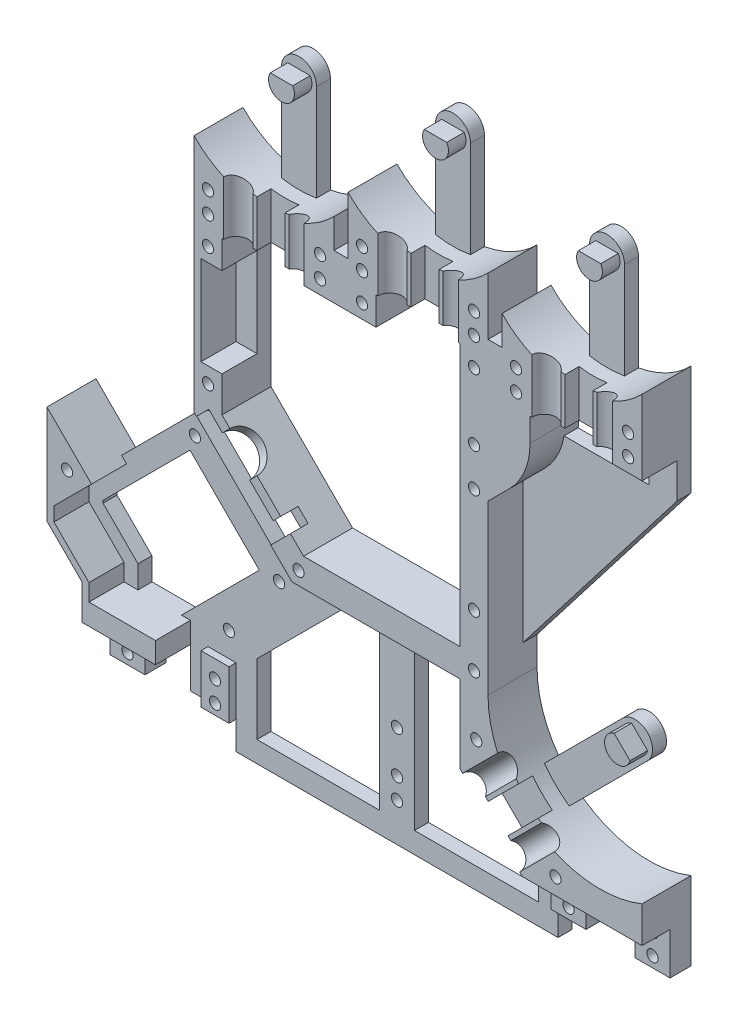
SolidWorks part; units mm, degrees
ref_plane "Front" through (0, 0, 0) normal (0, 0, 1) x (1, 0, 0)
ref_plane "Top" through (0, 0, 0) normal (0, 1, 0) x (1, 0, 0)
ref_plane "Right" through (0, 0, 0) normal (1, 0, 0) x (0, 0, -1)
sketch "Sketch1" plane through (0, 0, 0) normal (0, 0, 1) x (1, 0, 0)
  line L0 (47, 67.5) -> (47, 71.5)
  line L1 (47, 71.5) -> (59, 71.5)
  line L2 (69, 67.5) -> (69, 62.5)
  line L3 (85, 10) -> (85, 15.1676)
  line L4 (67.8873, 10) -> (85, 10)
  line L5 (69, 67.5) -> (81, 67.5)
  line L6 (59, 71.5) -> (59, 34)
  line L7 (36.6568, 34) -> (59, 34)
  line L8 (5, 10) -> (5, 15)
  line L9 (15.4289, 34.0147) -> (3, 21.5858)
  line L10 (0, 34.1421) -> (0, 20)
  line L11 (25, 67.5) -> (25, 45.6568)
  line L12 (25, 45.6568) -> (36.6568, 34)
  line L13 (0, 20) -> (5, 15)
  line L14 (8, 13) -> (14.2134, 13)
  line L15 (25.3285, 24.1151) -> (14.2134, 13)
  line L16 (3, 21.2426) -> (3, 21.5858)
  line L17 (8, 13) -> (8, 16.2426)
  line L18 (81, 67.5) -> (81, 62.5)
  line L20 (3, 21.2426) -> (8, 16.2426)
  line L21 (81, 62.5) -> (69, 62.5)
  line L22 (65.2114, 12.6759) -> (59, 18.8873)
  line L24 (59, 18.8873) -> (59, 30)
  line L25 (47.5, 30) -> (59, 30)
  line L26 (63, 34) -> (85, 62.5)
  line L27 (65.2114, 3) -> (65.2114, 12.6759)
  line L30 (85, 71.5) -> (85, 62.5)
  line L31 (63, 34) -> (63, 30)
  line L77 (5.6569, 28.4853) -> (0, 34.1421)
  line L82 (25, 3) -> (25, 13)
  line L83 (22, 10) -> (5, 10)
  line L89 (16.136, 38.9644) -> (5.6569, 28.4853)
  line L109 (28.1568, 26.9436) -> (16.136, 38.9644)
  line L120 (21, 71.5) -> (21, 43.9999)
  line L127 (68, 0) -> (22, 0)
  line L129 (15.4289, 34.0147) -> (25.3285, 24.1151)
  line L132 (21, 43.9999) -> (33.1066, 31.8933)
  line L133 (21, 71.5) -> (43, 71.5)
  line L134 (25, 13) -> (42, 30)
  line L135 (22, 0) -> (22, 10)
  line L136 (68, 10) -> (68, 0)
  line L137 (85, 10) -> (68, 10)
  line L138 (25, 67.5) -> (47, 67.5)
  line L140 (43, 71.5) -> (43, 75.5)
  line L143 (42, 30) -> (42.5, 30)
  line L144 (63, 71.5) -> (85, 71.5)
  line L145 (63, 75.5) -> (63, 71.5)
  line L148 (33.1066, 31.8933) -> (28.1568, 26.9436)
  line L150 (47.5, 30) -> (47.5, 3)
  line L152 (42.5, 30) -> (42.5, 3)
  line L153 (43, 75.5) -> (63, 75.5)
  line L156 (47.5, 3) -> (65.2114, 3)
  line L157 (25, 3) -> (42.5, 3)
  line L160 (22, 0) -> (0, 0) construction
  arc A0 (63, 30) -> (85, 15.1676) centre (79, 30) ccw
extrude "Boss-Extrude1" add sketch "Sketch1" along normal blind 2 contours L83 L135 L127 L136 L137 L144 L145 L153 L140 L133 L120 L132 L148 L109 L89 L77 L157 L82 L134 L143 L152 L156 L150 L138 L129 region at (76.5, 11.1369, 0)
sketch "Sketch5" plane through (0, 0, 0) normal (0, 0, 1) x (1, 0, 0)
  line L0 (21, 78.202) -> (21, 43.9999)
  line L1 (63, 74) -> (65, 74)
  line L2 (80, 0) -> (73, 0) construction
  line L3 (15.5, 11) -> (15.5, 13)
  line L4 (43, 74) -> (43, 82.202)
  line L5 (63, 74) -> (63, 82.202)
  line L6 (69, 67.5) -> (85, 67.5)
  line L7 (5, 4) -> (5, 15)
  line L8 (22, 63.5) -> (22, 50.7322)
  line L9 (59, 30) -> (59, 18.8873)
  line L10 (53, 78) -> (53, 92) construction
  line L11 (25, 45.6568) -> (36.6568, 34)
  line L12 (12.6005, 43.2071) -> (12.2469, 43.5607) construction
  line L13 (32.3995, 31.8934) -> (16.8431, 47.4498) construction
  line L14 (15.5, 13) -> (6, 13)
  line L15 (0, 20) -> (5, 15)
  line L16 (73, 0) -> (73, -10) construction
  line L17 (17, 0) -> (17, -10) construction
  line L18 (12.2469, 43.5607) -> (2.3474, 33.6612) construction
  line L19 (73, -10) -> (68, -10) construction
  line L20 (28.1568, 27.6508) -> (12.6005, 43.2071) construction
  line L21 (68, -10) -> (68, 0) construction
  line L22 (0, 34.1422) -> (6.364, 27.7783)
  line L23 (0, 34.1422) -> (0, 20)
  line L24 (6, 13) -> (6, 15.4142)
  line L25 (19, 64.2929) -> (-1, 64.2929) construction
  line L26 (17, -10) -> (22, -10) construction
  line L27 (85, 0) -> (85, -10) construction
  line L28 (-1, 37.0086) -> (-1, 64.2929) construction
  line L29 (5, 4) -> (10, 4)
  line L30 (22, -10) -> (22, 0) construction
  line L31 (85, -10) -> (80, -10) construction
  line L32 (0, 0) -> (5, 0) construction
  line L33 (10, 4) -> (10, 10)
  line L34 (80, -10) -> (80, 0) construction
  line L35 (34.9999, 30) -> (59, 30)
  line L36 (80, 0) -> (85, 0) construction
  line L37 (85, 4) -> (80, 4)
  line L38 (22, 4) -> (22, 11)
  line L39 (10, 10) -> (15.5, 10)
  line L40 (15.5, 10) -> (15.5, 4)
  line L41 (42.5, 10) -> (47.5, 10) construction
  line L42 (80, 4) -> (80, 10)
  line L43 (31, 74) -> (31, 88) construction
  line L44 (10, 0) -> (17, 0) construction
  line L45 (17, 0) -> (22, 0) construction
  line L46 (34.9999, 30) -> (21, 43.9999)
  line L47 (36.6568, 34) -> (59, 34)
  line L48 (73, 10) -> (73, 4)
  line L49 (80, 10) -> (73, 10)
  line L50 (73, 4) -> (68, 4)
  line L51 (85, 67.5) -> (85, 78.202)
  line L52 (73, 0) -> (68, 0) construction
  line L53 (2.3474, 33.6612) -> (-1, 37.0086) construction
  line L54 (28.1568, 27.6508) -> (32.3995, 31.8934) construction
  line L55 (15.5, 4) -> (22, 4)
  line L56 (59, 18.8873) -> (65.2114, 12.6759)
  line L57 (42.5, 0) -> (42.5, 10) construction
  line L58 (42.5, 0) -> (42.5, -10) construction
  line L59 (65.2114, 12.6759) -> (68, 9.8873)
  line L60 (59, 34) -> (59, 71.5)
  line L61 (42.5, 10) -> (47.5, 10) construction
  line L62 (47.5, -10) -> (47.5, 0) construction
  line L63 (47.5, 10) -> (47.5, 0) construction
  line L64 (42.5, -10) -> (47.5, -10) construction
  line L65 (15.5, 11) -> (22, 11)
  line L66 (25, 67.5) -> (47, 67.5)
  line L67 (47, 67.5) -> (47, 71.5)
  line L68 (19, 45.2929) -> (19, 64.2929) construction
  line L69 (25, 45.6568) -> (25, 50.7322)
  line L70 (63, 54) -> (63, 30)
  line L71 (25, 67.5) -> (25, 63.5)
  line L72 (25, 63.5) -> (22, 63.5)
  line L74 (25, 50.7322) -> (22, 50.7322)
  line L75 (68, 9.8873) -> (68, 4)
  line L76 (41, 74) -> (43, 74)
  line L79 (47, 71.5) -> (59, 71.5)
  line L80 (69, 67.5) -> (69, 60)
  line L82 (6.364, 27.7783) -> (1, 22.4143)
  line L83 (85, 15.1676) -> (85, 10)
  line L85 (85, 0) -> (80, 0) construction
  line L86 (85, 0) -> (85, -10) construction
  line L87 (1, 20.4142) -> (6, 15.4142)
  line L88 (42.5, -10) -> (47.5, -10) construction
  line L89 (80, 0) -> (73, 0) construction
  line L90 (85, -10) -> (80, -10) construction
  line L91 (80, -10) -> (80, 0) construction
  line L93 (5, 0) -> (5, -10) construction
  line L94 (68, -10) -> (68, 0) construction
  line L95 (41, 78.202) -> (41, 74)
  line L96 (5, -10) -> (10, -10) construction
  line L97 (73, 0) -> (73, -10) construction
  line L98 (73, -10) -> (68, -10) construction
  line L99 (10, -10) -> (10, 0) construction
  line L100 (10, 0) -> (5, 0) construction
  line L101 (5, 0) -> (10, 0) construction
  line L102 (10, 0) -> (17, 0) construction
  line L103 (73, 0) -> (68, 0) construction
  line L104 (75, 74) -> (75, 88) construction
  line L105 (65, 74) -> (65, 78.202)
  line L106 (22, -10) -> (17, -10) construction
  line L107 (17, -10) -> (17, 0) construction
  line L108 (1, 22.4143) -> (1, 20.4142)
  line L109 (22, 0) -> (17, 0) construction
  line L110 (22, -10) -> (22, 0) construction
  line L111 (68, 0) -> (47.5, 0) construction
  line L112 (47.5, 0) -> (47.5, -10) construction
  line L113 (42.5, -10) -> (42.5, 0) construction
  line L114 (42.5, 0) -> (22, 0) construction
  line L115 (63, 54) -> (69, 60)
  line L116 (85, 10) -> (85, 4)
  arc A0 (21, 78.202) -> (41, 78.202) centre (31, 88) ccw
  arc A1 (43, 82.202) -> (63, 82.202) centre (53, 92) ccw
  arc A2 (65, 78.202) -> (85, 78.202) centre (75, 88) ccw
  arc A3 (63, 30) -> (85, 15.1676) centre (79, 30) ccw
extrude "Boss-Extrude2" add sketch "Sketch5" along normal blind 7 contours A2 L105 L1 L5 A1 L4 L76 L95 A0 L51 L79 L60 L74 L8 L72 L71 | L108 L23 L15 L7 L29 L33 L39 L40 L55 L38 L87 | L50 L48 L49 L42 L37 region at (31, 72.9895, 0) region at (18.75, 10.6268, 0)
sketch "Sketch33" plane through (0, 0, 0) normal (0, 0, 1) x (1, 0, 0)
  line L1 (31, 74) -> (31, 67.5) construction
  line L2 (31, 74) -> (31, 67.5) construction
  line L3 (75, 74) -> (75, 67.5) construction
  line L4 (31, 67.5) -> (33.5, 67.5)
  line L5 (75, 67.5) -> (77.5, 67.5)
  line L6 (77.5, 67.5) -> (77.5, 88)
  line L7 (75, 67.5) -> (72.5, 67.5)
  line L8 (72.5, 67.5) -> (72.5, 88)
  line L9 (77.2322, 31.7678) -> (61.6759, 16.2114)
  line L11 (61.6759, 16.2114) -> (65.2114, 12.6759)
  line L13 (53, 78) -> (53, 71.5) construction
  line L14 (53, 71.5) -> (55.5, 71.5)
  line L15 (55.5, 71.5) -> (55.5, 92)
  line L16 (53, 71.5) -> (50.5, 71.5)
  line L17 (50.5, 71.5) -> (50.5, 92)
  line L18 (33.5, 67.5) -> (33.5, 88)
  line L19 (31, 67.5) -> (28.5, 67.5)
  line L20 (28.5, 67.5) -> (28.5, 88)
  line L21 (65.2114, 12.6759) -> (80.7678, 28.2322)
  arc A0 (77.5, 88) -> (72.5, 88) centre (75, 88) ccw
  arc A1 (55.5, 92) -> (50.5, 92) centre (53, 92) ccw
  arc A2 (33.5, 88) -> (28.5, 88) centre (31, 88) ccw
  arc A3 (80.7678, 28.2322) -> (77.2322, 31.7678) centre (79, 30) ccw
extrude "Boss-Extrude3" add sketch "Sketch33" along normal blind 2
sketch "Sketch34" plane through (0, 0, 0) normal (0, 0, 1) x (1, 0, 0)
  line L0 (31, 88) -> (31, 88.925) construction
  line L1 (29.3979, 88.925) -> (32.6021, 88.925)
  line L2 (53, 92) -> (53, 92.925) construction
  line L3 (51.3979, 92.925) -> (54.6021, 92.925)
  line L4 (75, 88) -> (75, 88.925) construction
  line L5 (73.3979, 88.925) -> (76.6021, 88.925)
  line L6 (79, 30) -> (79.6541, 30.6541) construction
  line L7 (78.5212, 31.787) -> (80.787, 29.5212)
  arc A0 (78.5212, 31.787) -> (80.787, 29.5212) centre (79, 30) ccw
  arc A3 (29.3979, 88.925) -> (32.6021, 88.925) centre (31, 88) ccw
  arc A4 (51.3979, 92.925) -> (54.6021, 92.925) centre (53, 92) ccw
  arc A5 (73.3979, 88.925) -> (76.6021, 88.925) centre (75, 88) ccw
extrude "Boss-Extrude4" add sketch "Sketch34" along normal blind 2.5 from offset 2
sketch "Sketch10" plane through (0, 0, 0) normal (0, 1, 0) x (1, 0, 0)
  line L0 (49, -7) -> (57, -7)
  line L1 (27, -6) -> (29, -6)
  line L2 (35, -7) -> (35, -6)
  line L3 (27, -7) -> (35, -7)
  line L4 (71, -7) -> (79, -7)
  line L5 (49, -6) -> (51, -6)
  line L6 (27, -6) -> (27, -7)
  line L7 (29, -6) -> (29, -4)
  line L8 (29, -4) -> (33, -4)
  line L9 (57, -7) -> (57, -6)
  line L10 (33, -4) -> (33, -6)
  line L11 (71, -6) -> (73, -6)
  line L12 (33, -6) -> (35, -6)
  line L13 (51, -6) -> (51, -4)
  line L14 (51, -4) -> (55, -4)
  line L15 (55, -4) -> (55, -6)
  line L16 (55, -6) -> (57, -6)
  line L17 (73, -6) -> (73, -4)
  line L18 (73, -4) -> (77, -4)
  line L19 (77, -4) -> (77, -6)
  line L20 (77, -6) -> (79, -6)
  line L23 (49, -6) -> (49, -7)
  line L32 (79, -7) -> (79, -6)
  line L47 (71, -6) -> (71, -7)
  circle A0 centre (27, -7) radius 1.75
  circle A1 centre (35, -7) radius 1.75
  circle A2 centre (49, -7) radius 1.75
  circle A3 centre (57, -7) radius 1.75
  circle A4 centre (71, -7) radius 1.75
  circle A5 centre (79, -7) radius 1.75
extrude "Wire and Tube Canals" cut sketch "Sketch10" along normal blind 13 from offset 67.5 contours A0 | A1 | A2 | A3 | A4 | A5 | A3 A2 L0 | A5 A4 L4 | L3 L2 L12 L10 L8 L7 L1 L6 region at (48.8288, 0, 7.1002) region at (53, 0, 5.5512) region at (57.1712, 0, 7.1002) region at (26.8288, 0, 7.1002) region at (35.1712, 0, 7.1002) region at (70.8288, 0, 7.1002) region at (75, 0, 5.5512) region at (79.1712, 0, 7.1002) body kept at (59, 30, 0)
sketch "Sketch42" plane through (0, 0, 0) normal (0, 0, 1) x (1, 0, 0)
  line L1 (5, 4) -> (10, 4)
  line L2 (5, 4) -> (5, 10)
  line L3 (5, 10) -> (10, 10)
  line L4 (10, 4) -> (10, 10)
  line L5 (15.5, 4) -> (22, 4)
  line L6 (15.5, 4) -> (15.5, 11)
  line L7 (15.5, 11) -> (22, 11)
  line L8 (22, 4) -> (22, 11)
  line L10 (67, 4) -> (73, 4)
  line L11 (67, 4) -> (67, 10)
  line L12 (67, 10) -> (73, 10)
  line L13 (73, 4) -> (73, 10)
  line L14 (80, 4) -> (85, 4)
  line L15 (80, 4) -> (80, 10)
  line L16 (80, 10) -> (85, 10)
  line L17 (85, 4) -> (85, 10)
extrude "Cut-Extrude3" cut sketch "Sketch42" along normal blind 4 from offset 3
fillet "Fillet1" radius 10 1 edges at (69, 60, 4.5)
sketch "Sketch35" plane through (32.4999, 32.4999, 0) normal (-0.7071, -0.7071, 0) x (0, 0, 1)
  line L0 (7, 15.7634) -> (7, 10.2634) construction
  line L1 (7, 10.2634) -> (7, 0.7634) construction
  line L2 (7, 10.2634) -> (12.5, 10.2634) construction
  line L3 (7, 10.2634) -> (1.5, 10.2634) construction
  line L4 (5.5, 15.7634) -> (5.5, 14.2634) construction
  line L5 (5.5, 14.2634) -> (2.5, 14.2634) construction
  line L6 (5.5, 15.7634) -> (2.5, 14.2634)
  line L7 (2.5, 14.2634) -> (1.5, 14.2634)
  line L8 (1.5, 14.2634) -> (1.5, 10.2634)
  line L9 (1.5, 10.2634) -> (1.5, 6.0134)
  line L10 (1.5, 6.0134) -> (2.5, 6.0134)
  line L11 (2.5, 6.0134) -> (2.5, 0.7634)
  line L12 (2.5, 0.7634) -> (7, 0.7634)
  line L13 (8.5, 15.7634) -> (8.5, 14.2634) construction
  line L14 (8.5, 14.2634) -> (11.5, 14.2634) construction
  line L15 (8.5, 15.7634) -> (11.5, 14.2634)
  line L16 (11.5, 14.2634) -> (12.5, 14.2634)
  line L17 (12.5, 14.2634) -> (12.5, 10.2634)
  line L18 (12.5, 10.2634) -> (12.5, 6.0134)
  line L19 (12.5, 6.0134) -> (11.5, 6.0134)
  line L20 (11.5, 6.0134) -> (11.5, 0.7634)
  line L21 (11.5, 0.7634) -> (7, 0.7634)
  line L22 (12, 10.2634) -> (7, 10.2634) construction
  line L23 (8.5, 15.7634) -> (7, 15.7634)
  line L24 (7, 15.7634) -> (5.5, 15.7634)
  line L25 (7, 15.7634) -> (7, 16.2634) construction
  line L26 (2, 10.2634) -> (7, 10.2634) construction
extrude "Pot Insert1" cut sketch "Sketch35" against normal blind 2.5
sketch "Sketch36" plane through (32.4999, 32.4999, 0) normal (-0.7071, -0.7071, 0) x (0, 0, 1)
  line L0 (7, 16.2634) -> (7, 10.2634) construction
  line L1 (7, 10.2634) -> (7, 0.7634) construction
  line L2 (7, 0.7634) -> (4.5, 0.7634)
  line L5 (4.5, 0.7634) -> (4.5, 2.7634)
  line L6 (7, 0.7634) -> (9.5, 0.7634)
  line L7 (9.5, 0.7634) -> (9.5, 2.7634)
  line L8 (9.5, 2.7634) -> (4.5, 2.7634)
  circle A0 centre (7, 10.2634) radius 2.75
extrude "Pot Hole" cut sketch "Sketch36" against normal blind 1.5 from offset 2.5
sketch "Sketch43" plane through (15.5, 0, 0) normal (-1, 0, 0) x (0, 0, 1)
  line L0 (6.5, -5.5) -> (6.5, 0) construction
  line L1 (6.5, 0) -> (6.5, 11) construction
  line L2 (6.5, 0) -> (1, 0) construction
  line L3 (6.5, 0) -> (12, 0) construction
  line L4 (8, -5.5) -> (8, -4) construction
  line L5 (8, -4) -> (11, -4) construction
  line L6 (8, -5.5) -> (11, -4)
  line L7 (11, -4) -> (12, -4)
  line L8 (12, -4) -> (12, 0)
  line L9 (12, 0) -> (12, 5.25)
  line L10 (12, 5.25) -> (11, 5.25)
  line L11 (11, 5.25) -> (11, 11)
  line L12 (11, 11) -> (6.5, 11)
  line L13 (5, -5.5) -> (5, -4) construction
  line L14 (5, -4) -> (2, -4) construction
  line L15 (5, -5.5) -> (2, -4)
  line L16 (2, -4) -> (1, -4)
  line L17 (1, -4) -> (1, 0)
  line L18 (1, 0) -> (1, 4.25)
  line L19 (1, 4.25) -> (2, 4.25)
  line L20 (2, 4.25) -> (2, 11)
  line L21 (2, 11) -> (6.5, 11)
  line L22 (1.5, 0) -> (6.5, 0) construction
  line L23 (5, -5.5) -> (6.5, -5.5)
  line L24 (6.5, -5.5) -> (8, -5.5)
  line L25 (11.5, 0) -> (6.5, 0) construction
extrude "Pot Insert2" cut sketch "Sketch43" against normal blind 2.5
sketch "Sketch3" plane through (0, 0, 0) normal (0, 0, 1) x (1, 0, 0)
  line L0 (31, 72.5) -> (31, 69.5) construction
  line L1 (31, 69.5) -> (31, 65.5) construction
  line L2 (75, 69.5) -> (75, 65.5) construction
  line L3 (31, 65.5) -> (23, 65.5) construction
  line L4 (33.1066, 31.8933) -> (34.5208, 30.4791) construction
  line L5 (53, 69.5) -> (45, 69.5) construction
  line L6 (53, 73.5) -> (53, 69.5) construction
  line L7 (53, 69.5) -> (61, 69.5) construction
  line L9 (67.6863, 18.6863) -> (66.9792, 17.9792) construction
  line L10 (53, 69.5) -> (53, 54.5) construction
  line L11 (75, 65.5) -> (75, 48.75) construction
  line L12 (66.9792, 17.9792) -> (61.3223, 23.636) construction
  line L13 (31, 69.5) -> (39, 69.5) construction
  line L14 (66.9792, 17.9792) -> (72.636, 12.3223) construction
  line L15 (53, 76.5) -> (53, 73.5) construction
  line L16 (16.136, 38.9645) -> (17.5502, 37.5503) construction
  line L17 (75, 74) -> (75, 72.5) construction
  line L18 (75, 72.5) -> (83, 72.5) construction
  line L19 (75, 72.5) -> (67, 72.5) construction
  line L20 (34.5208, 30.4791) -> (35.935, 31.8933) construction
  line L21 (53, 76.5) -> (61, 76.5) construction
  line L22 (53, 76.5) -> (45, 76.5) construction
  line L23 (31, 74) -> (31, 72.5) construction
  line L24 (31, 72.5) -> (39, 72.5) construction
  line L25 (31, 72.5) -> (23, 72.5) construction
  line L26 (75, 72.5) -> (75, 69.5) construction
  line L27 (75, 69.5) -> (83, 69.5) construction
  line L28 (75, 69.5) -> (67, 69.5) construction
  line L29 (53, 73.5) -> (61, 73.5) construction
  line L30 (53, 73.5) -> (45, 73.5) construction
  line L31 (31, 69.5) -> (23, 69.5) construction
  line L32 (53, 54.5) -> (61, 54.5) construction
  line L36 (75, 48.75) -> (75, 32) construction
  line L38 (17.5502, 37.5503) -> (16.136, 36.1361) construction
  line L39 (31, 55.5) -> (31, 65.5) construction
  line L42 (61, 39.5) -> (53, 39.5) construction
  line L43 (53, 39.5) -> (53, 54.5) construction
  line L45 (31, 55.5) -> (31, 48.5) construction
  line L51 (31, 48.5) -> (23, 48.5) construction
  line L54 (82.5, 4) -> (82.5, 5.5) construction
  line L55 (28.1568, 26.9437) -> (29.571, 25.5295) construction
  line L56 (82.5, 5.5) -> (82.5, 8.5) construction
  line L57 (7.5, 4) -> (7.5, 5.5) construction
  line L58 (29.571, 25.5295) -> (28.1568, 24.1153) construction
  line L60 (70.5, 4) -> (70.5, 5.5) construction
  line L61 (70.5, 5.5) -> (70.5, 8.5) construction
  line L62 (53, 39.5) -> (53, 32) construction
  line L63 (7.5, 5.5) -> (7.5, 8.5) construction
  line L64 (53, 32) -> (61, 32) construction
  line L65 (45, 10) -> (45, 8.5) construction
  line L67 (20, 4) -> (20, 5.5) construction
  line L68 (20, 5.5) -> (20, 8.5) construction
  line L70 (45, 8.5) -> (45, 5.5) construction
  line L73 (6.364, 27.7783) -> (2.864, 27.7783) construction
  circle A0 centre (67, 72.5) radius 0.8
  circle A1 centre (83, 72.5) radius 0.8
  circle A2 centre (61, 76.5) radius 0.8
  circle A3 centre (45, 76.5) radius 0.8
  circle A4 centre (23, 72.5) radius 0.8
  circle A5 centre (39, 72.5) radius 0.8
  circle A6 centre (83, 69.5) radius 0.8
  circle A7 centre (67, 69.5) radius 0.8
  circle A8 centre (61, 73.5) radius 0.8
  circle A9 centre (45, 73.5) radius 0.8
  circle A10 centre (23, 69.5) radius 0.8
  circle A11 centre (39, 69.5) radius 0.8
  circle A13 centre (35.935, 31.8933) radius 0.8
  circle A14 centre (61.3223, 23.636) radius 0.8
  circle A15 centre (23, 65.5) radius 0.8
  circle A16 centre (45, 69.5) radius 0.8
  circle A17 centre (61, 69.5) radius 0.8
  circle A18 centre (72.636, 12.3223) radius 0.8
  circle A21 centre (61, 54.5) radius 0.8
  circle A24 centre (16.136, 36.1361) radius 0.8
  circle A25 centre (28.1568, 24.1153) radius 0.8
  circle A26 centre (23, 48.5) radius 0.8
  circle A29 centre (61, 39.5) radius 0.8
  circle A32 centre (45, 8.5) radius 0.8
  circle A36 centre (82.5, 5.5) radius 0.8
  circle A37 centre (82.5, 8.5) radius 0.8
  circle A38 centre (70.5, 5.5) radius 0.8
  circle A39 centre (70.5, 8.5) radius 0.8
  circle A40 centre (7.5, 5.5) radius 0.8
  circle A41 centre (7.5, 8.5) radius 0.8
  circle A42 centre (20, 5.5) radius 0.8
  circle A43 centre (20, 8.5) radius 0.8
  circle A44 centre (61, 32) radius 0.8
  circle A45 centre (45, 5.5) radius 0.8
  circle A46 centre (2.864, 27.7783) radius 0.8
extrude "Mechanical Screw Holes" cut sketch "Sketch3" along normal through all
sketch "Sketch44" plane through (0, 0, 0) normal (0, 0, 1) x (1, 0, 0)
  line L0 (45, 8.5) -> (45, 14.5) construction
  circle A0 centre (61, 60) radius 0.8
  circle A1 centre (21, 14.5) radius 0.8
  circle A2 centre (45, 14.5) radius 0.8
extrude "Electrical Screw Holes" cut sketch "Sketch44" along normal through all
sketch "Sketch45" plane through (38.9437, 38.9437, 0) normal (-0.7071, -0.7071, 0) x (0, 0, 1)
  line L0 (6, -38.6482) -> (7, -38.6482)
  line L1 (6, -30.6482) -> (6, -32.6482)
  line L2 (7, -38.6482) -> (7, -30.6482)
  line L3 (7, -30.6482) -> (6, -30.6482)
  line L4 (6, -32.6482) -> (4, -32.6482)
  line L5 (6, -36.6482) -> (4, -36.6482)
  line L6 (4, -36.6482) -> (4, -32.6482)
  line L7 (6, -36.6482) -> (6, -38.6482)
  circle A0 centre (7, -30.6482) radius 1.75
  circle A1 centre (7, -38.6482) radius 1.75
  line M2 (7, -40.9325) -> (7, -28.364)
extrude "Cut-Extrude4" cut sketch "Sketch45" against normal blind 10 contours A1 L0 M2 | A0 L3 M2 | A1 L2 A0 | A0 L2 L3 | A1 L0 M2 region at (65.6871, 12.2002, 6.5155) region at (66.5773, 11.31, 6.1225) region at (63.4437, 14.4437, 5.5512) region at (61.2002, 16.6871, 6.5155) region at (60.31, 17.5773, 6.1225)
